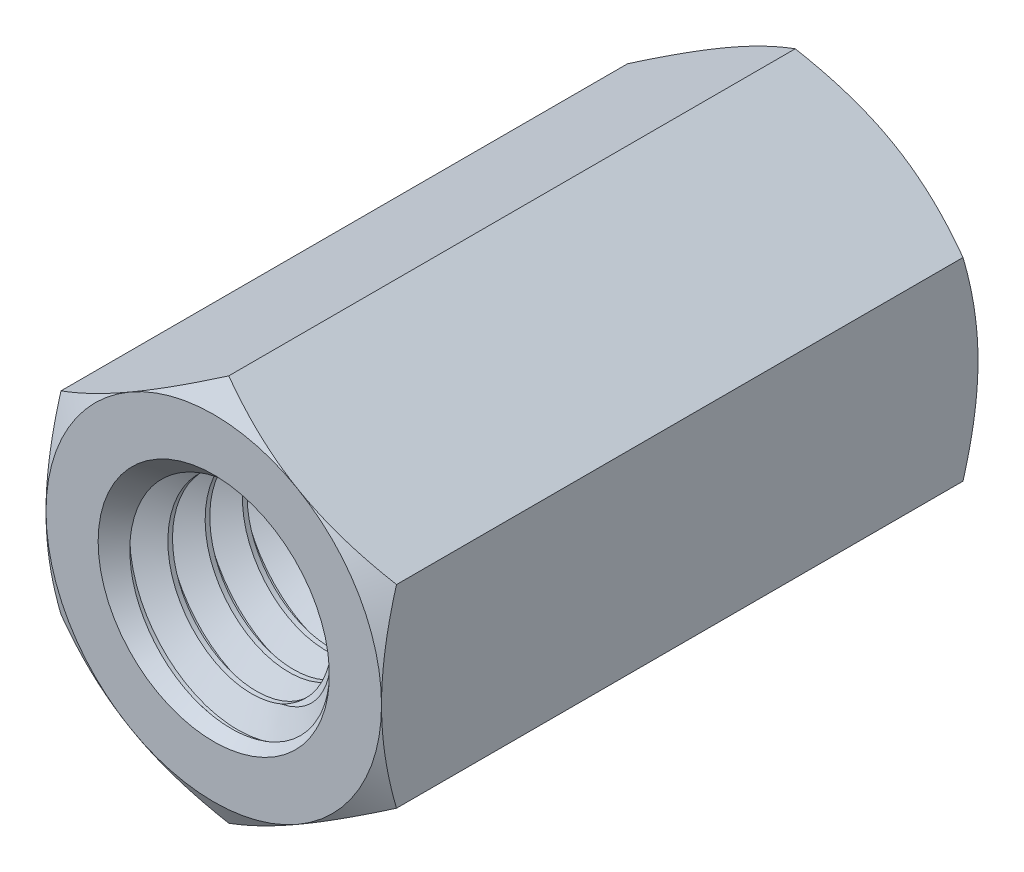
SolidWorks part; units mm, degrees
ref_plane "Front Plane" through (0, 0, 0) normal (0, 0, 1) x (1, 0, 0)
ref_plane "Top Plane" through (0, 0, 0) normal (0, 1, 0) x (1, 0, 0)
ref_plane "Right Plane" through (0, 0, 0) normal (1, 0, 0) x (0, 0, -1)
sketch "Sketch3" plane through (0, 0, 0) normal (1, 0, 0) x (0, 0, -1)
  line L0 (-4, 0) -> (4, 0) construction
  line L1 (0, 2.25) -> (0, -2.25) construction
  line L2 (-4, 1.5) -> (-4, -1.5) construction
  point P2 (-0.8, 0)
  point P3 (0.8, 0)
  dimension "Length" = 8
  dimension "Min Thread Length" = 4.8
  dimension "D1" = 4.8
  dimension "Thread Dia" = 3
  dimension "Hex" = 4.5
sketch "Sketch1" plane through (0, 0, 0) normal (0, 0, 1) x (1, 0, 0)
  line L1 (0, 2.5981) -> (-2.25, 1.299)
  line L2 (-2.25, 1.299) -> (-2.25, -1.299)
  line L3 (-2.25, -1.299) -> (0, -2.5981)
  line L4 (0, -2.5981) -> (2.25, -1.299)
  line L5 (2.25, -1.299) -> (2.25, 1.299)
  line L6 (2.25, 1.299) -> (0, 2.5981)
  circle A0 centre (0, 0) radius 2.25 construction
  circle A1 centre (0, 0) radius 1.5
extrude "Extrude1" add sketch "Sketch1" along normal up to vertex (4 mm away) and the other way up to vertex (4 mm away) up to point (0, 0, 4) other way up to point (0, 0, -4)
sketch "Sketch11" plane through (0, 0, -4) normal (0, 0, -1) x (-1, 0, 0)
  circle A0 centre (0, 0) radius 1.5 construction
  circle A1 centre (0, 0) radius 1.5
curve "Helix/Spiral1" pitch 0.5 height 8.5 radius 1.5 centre (0, 0, -4) axis (0, 0, 1) start towards (0, 1, 0) parameters "Pitch"=0.5
sketch "Sketch12" plane through (0, 0, 0) normal (1, 0, 0) x (0, 0, -1)
  line L0 (4.4375, 1.5) -> (4, 1.5)
  line L1 (4.4375, 1.5) -> (4.25, 1.1752)
  line L2 (4.25, 1.1752) -> (4.1875, 1.1752)
  line L3 (4.1875, 1.1752) -> (4, 1.5)
  line L4 (4.2187, 1.1752) -> (4.2187, 1.5) construction
  line L5 (4.3437, 1.3376) -> (4.0937, 1.3376) construction
  dimension "D1" = 0.0625
  dimension "D2" = 0.25
  dimension "D3" = 60
sweep "Sweep1" add profiles "Sketch12" path "Helix/Spiral1"
sketch "Sketch6" plane through (0, 0, -4) normal (0, 0, -1) x (-1, 0, 0)
  line L6 (0, 2.5981) -> (-2.25, 1.299)
  line L7 (-2.25, 1.299) -> (-2.25, -1.299)
  line L8 (-2.25, -1.299) -> (0, -2.5981)
  line L9 (0, -2.5981) -> (2.25, -1.299)
  line L10 (2.25, -1.299) -> (2.25, 1.299)
  line L11 (2.25, 1.299) -> (0, 2.5981)
  line L12 (0, 2.5981) -> (-2.25, 1.299)
  line L13 (-2.25, 1.299) -> (-2.25, -1.299)
  line L14 (-2.25, -1.299) -> (0, -2.5981)
  line L15 (0, -2.5981) -> (2.25, -1.299)
  line L16 (2.25, -1.299) -> (2.25, 1.299)
  line L17 (2.25, 1.299) -> (0, 2.5981)
  dimension "D1" = 0
extrude "Extrude2" cut sketch "Sketch6" along normal through all
sketch "Sketch7" plane through (0, 0, -4) normal (0, 0, -1) x (-1, 0, 0)
  circle A2 centre (0, 0) radius 1.5508
  circle A3 centre (0, 0) radius 1.5508
  dimension "D1" = 0.0508
extrude "Extrude3" cut sketch "Sketch7" against normal through all draft 43
sketch "Sketch8" plane through (0, 0, -4) normal (0, 0, -1) x (-1, 0, 0)
  circle A0 centre (0, 0) radius 2.25 construction
  circle A1 centre (0, 0) radius 2.25
extrude "Extrude4" cut sketch "Sketch8" against normal through all draft 60 flip side to cut
mirror "Mirror1" about plane through (0, 0, 0) normal (0, 0, 1) of "Extrude2", "Extrude3", "Extrude4"
sketch "Sketch9" [suppressed] plane through (0, 0, 0) normal (1, 0, 0) x (0, 0, -1)
  line L1 (-1.2, 1.1353) -> (1.2, 1.1353)
  line L2 (-1.2, 1.1353) -> (-1.2, 0)
  line L3 (-1.2, 0) -> (1.2, 0)
  line L4 (1.2, 1.1353) -> (1.2, 0)
  line L7 (-6, 0) -> (6, 0) construction
revolve "Revolve" [suppressed] add sketch "Sketch9" angle 360 about L0
sketch "Sketch10" [suppressed] plane through (0, 0, 0) normal (1, 0, 0) x (0, 0, -1)
  line L0 (6, 1.25) -> (1.2, 1.25)
  line L1 (-6, 1.25) -> (-1.2, 1.25)
  line L2 (1.2, 1.25) -> (1.2, -1.25)
  line L3 (-6, -1.25) -> (-1.2, -1.25)
  line L4 (-1.2, 1.25) -> (-1.2, -1.25)
  line L5 (1.2, -1.25) -> (6, -1.25)
equation "\"D1@Sketch3\" = \"Min Thread Length@Sketch3\""
equation "\"D3@Helix/Spiral1\" = \"Length@Sketch3\"+\"Pitch@Helix/Spiral1\""
equation "\"D1@Sketch12\" = \"Pitch@Helix/Spiral1\"*.125"
equation "\"D2@Sketch12\" = \"Pitch@Helix/Spiral1\"*.5"
